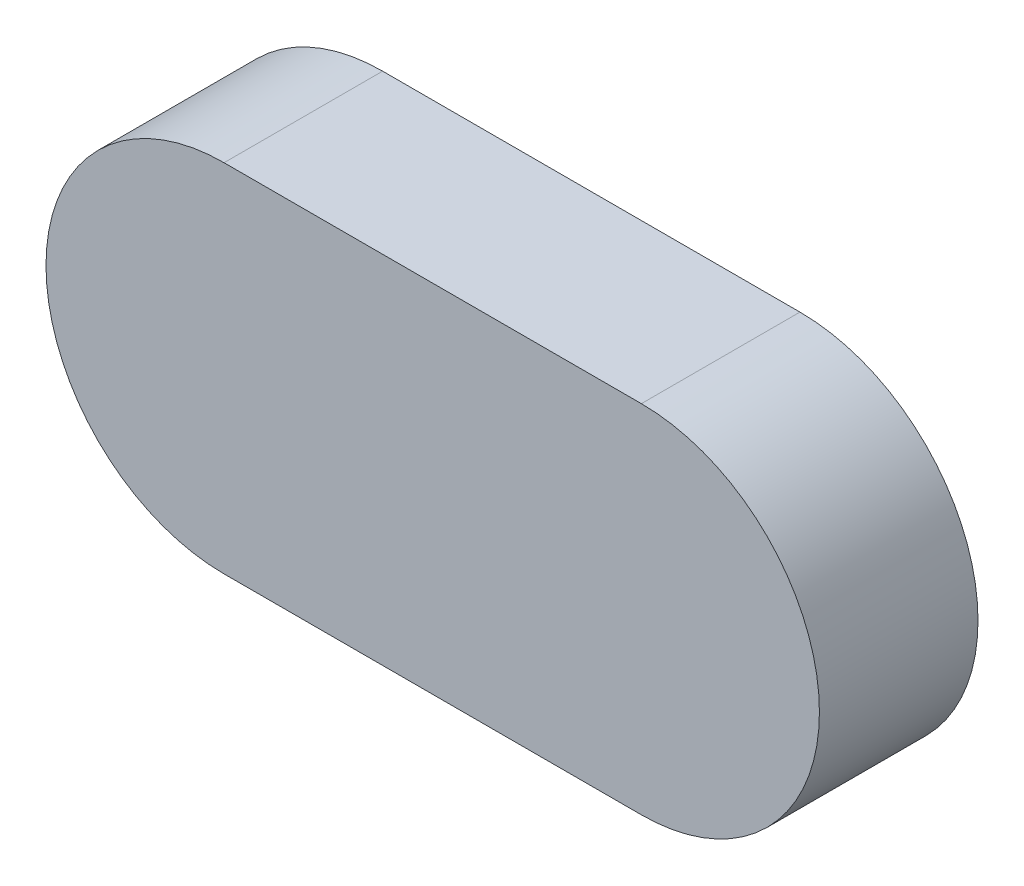
SolidWorks part; units mm, degrees
ref_plane "Front Plane" through (0, 0, 0) normal (0, 0, 1) x (1, 0, 0)
ref_plane "Top Plane" through (0, 0, 0) normal (0, 1, 0) x (1, 0, 0)
ref_plane "Right Plane" through (0, 0, 0) normal (1, 0, 0) x (0, 0, -1)
sketch "Sketch2" plane through (0, 0, 0) normal (0, 0, 1) x (1, 0, 0)
  line L0 (0, 64) -> (150, 64)
  line L1 (0, -64) -> (150, -64)
  circle A0 centre (0, 0) radius 54
  circle A1 centre (150, 0) radius 54
  circle A2 centre (0, 0) radius 64
  circle A3 centre (150, 0) radius 64
  dimension "D2" = 108
  dimension "D3" = 108
  dimension "D4" = 128
  dimension "D5" = 128
  dimension "D1" = 150
extrude "Boss-Extrude1" add sketch "Sketch2" against normal blind 57 contours A3 L0 A2 L1 | A3 A1 | A1 | A0 | A2 A0 region at (75, 0, 0) region at (43.9748, 43.9748, 0) region at (193.9748, 43.9748, 0) region at (0, 0, 0) region at (150, 0, 0)
sketch "Sketch3" plane through (0, 0, -57) normal (0, 0, -1) x (-1, 0, 0)
  circle A0 centre (0, 0) radius 54
  circle A1 centre (-150, 0) radius 54
  point P5 (0, 0)
  point P6 (0, 0)
  dimension "D2" = 108
  dimension "D3" = 108
  dimension "D1" = 150
extrude "Cut-Extrude1" cut sketch "Sketch3" against normal blind 42
sketch "Sketch4" plane through (0, 0, -15) normal (0, 0, -1) x (-1, 0, 0)
  line L0 (-180, -26.25) -> (-180, 26.25)
  line L1 (-26.25, -30) -> (26.25, -30)
  line L2 (-30, -26.25) -> (-30, 26.25)
  line L3 (-26.25, 30) -> (26.25, 30)
  line L4 (30, -26.25) -> (30, 26.25)
  line L5 (-30, -30) -> (30, 30) construction
  line L6 (-30, 30) -> (30, -30) construction
  line L7 (-176.25, 30) -> (-123.75, 30)
  line L8 (-120, -26.25) -> (-120, 26.25)
  line L9 (-176.25, -30) -> (-123.75, -30)
  arc A0 (30, -26.25) -> (26.25, -30) centre (26.25, -26.25) cw
  arc A1 (-30, -26.25) -> (-26.25, -30) centre (-26.25, -26.25) ccw
  arc A2 (-30, 26.25) -> (-26.25, 30) centre (-26.25, 26.25) cw
  arc A3 (30, 26.25) -> (26.25, 30) centre (26.25, 26.25) ccw
  arc A4 (-120, 26.25) -> (-123.75, 30) centre (-123.75, 26.25) ccw
  arc A5 (-180, -26.25) -> (-176.25, -30) centre (-176.25, -26.25) ccw
  arc A6 (-180, 26.25) -> (-176.25, 30) centre (-176.25, 26.25) cw
  arc A7 (-120, -26.25) -> (-123.75, -30) centre (-123.75, -26.25) cw
  point P0 (0, 0)
  dimension "D3" = 3.75
  dimension "D1" = 60
  dimension "D2" = 60
  dimension "D4" = 2
extrude "Cut-Extrude2" cut sketch "Sketch4" against normal blind 10
